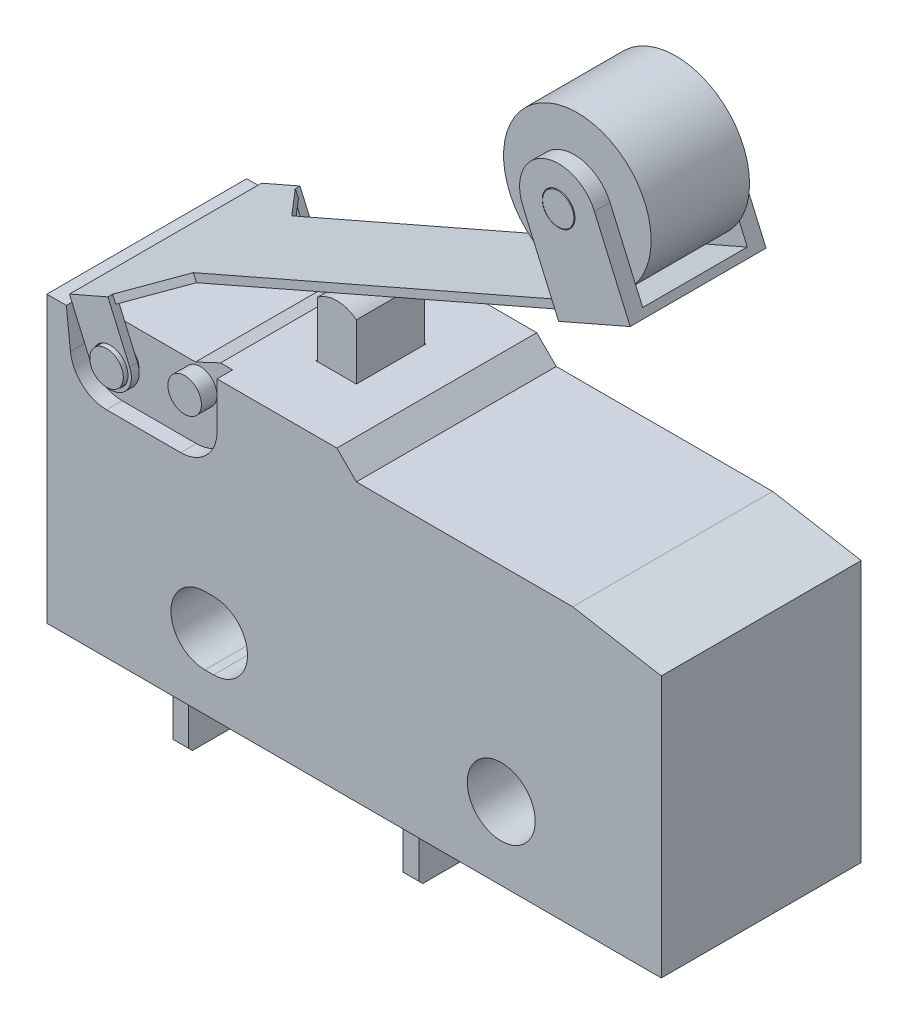
SolidWorks part; units mm, degrees
ref_plane "Front" through (0, 0, 0) normal (0, 0, 1) x (1, 0, 0)
ref_plane "Top" through (0, 0, 0) normal (0, 1, 0) x (1, 0, 0)
ref_plane "Right" through (0, 0, 0) normal (1, 0, 0) x (0, 0, -1)
sketch "Sketch2" plane through (0, 0, 0) normal (0, 0, 1) x (1, 0, 0)
  line L0 (-4.8514, 3.4671) -> (-4.572, 3.4671)
  line L1 (9.9949, 8.509) -> (7.1139, 9.017)
  line L2 (-9.9949, 9.271) -> (-9.9949, 0)
  line L3 (-9.9949, 0) -> (9.9949, 0)
  line L4 (9.9949, 8.509) -> (9.9949, 0)
  line L5 (-4.8514, 1.2573) -> (-4.572, 1.2573)
  line L6 (-4.7117, 3.4671) -> (-4.7117, 1.2573) construction
  line L7 (4.7879, 2.3622) -> (-4.572, 2.3622) construction
  line L8 (7.1139, 9.017) -> (0.0762, 9.017)
  line L9 (0.0762, 9.017) -> (-0.5588, 9.652)
  line L10 (-0.5588, 9.652) -> (-4.8514, 9.652)
  line L11 (-4.8514, 9.652) -> (-5.6646, 9.271)
  line L12 (-5.6646, 9.271) -> (-9.9949, 9.271)
  line L13 (-2.7051, 9.652) -> (-2.7051, 2.3622) construction
  line L14 (-4.8514, 9.652) -> (-4.8514, 3.4671) construction
  circle A0 centre (4.7879, 2.3622) radius 1.1049
  arc A1 (-4.8514, 3.4671) -> (-4.8514, 1.2573) centre (-4.8514, 2.3622) ccw
  arc A2 (-4.572, 1.2573) -> (-4.572, 3.4671) centre (-4.572, 2.3622) ccw
  dimension "D4" = 5.207
  dimension "D5" = 2.2098
  dimension "D6" = 2.4892
  dimension "D7" = 6.6548
  dimension "D8" = 7.2898
  dimension "D9" = 7.493
  dimension "D13" = 6.9088
  dimension "D1" = 19.9898
  dimension "D2" = 2.3622
  dimension "D3" = 9.4996
  dimension "D10" = 0.508
  dimension "D11" = 10
  dimension "D12" = 135
extrude "Extrude1" add sketch "Sketch2" along normal mid plane 6.5024
sketch "Sketch3" plane through (0, 0, 0) normal (0, 0, 1) x (1, 0, 0)
  line L0 (-3.3401, 9.271) -> (-3.3401, 11.4357)
  line L1 (-2.7051, 9.271) -> (-2.7051, 10.6426) construction
  line L2 (-2.0701, 11.4357) -> (-2.0701, 9.271)
  line L3 (-2.0701, 9.271) -> (-3.3401, 9.271)
  line L4 (-3.3401, 11.4357) -> (-2.0701, 11.4357) construction
  line L5 (-2.7051, 9.652) -> (-2.7051, 2.3622) construction
  line L6 (-5.6646, 9.271) -> (-9.9949, 9.271) construction
  arc A0 (-3.3401, 11.4357) -> (-2.0701, 11.4357) centre (-2.7051, 10.6426) cw
  arc A1 (-4.8514, 3.4671) -> (-4.8514, 1.2573) centre (-4.8514, 2.3622) ccw construction
  dimension "D1" = 9.2964
  dimension "D3" = 1.016
  dimension "D2" = 1.27
extrude "Extrude2" add sketch "Sketch3" along normal mid plane 2.2098 separate body
sketch "Sketch4" plane through (0, 9.652, 0) normal (0, 1, 0) x (-1, 0, 0)
  line L0 (2.0701, -1.1049) -> (3.3401, -1.1049) construction
  line L1 (3.3401, 1.1049) -> (3.3401, -1.1049) construction
  line L2 (2.0701, 1.1049) -> (2.0701, -1.1049) construction
  line L3 (3.3401, 1.1049) -> (2.0701, 1.1049) construction
  line L4 (2.0701, -1.1049) -> (3.3401, -1.1049) construction
  line L5 (3.3401, 1.1049) -> (3.3401, -1.1049) construction
  line L6 (2.0701, 1.1049) -> (2.0701, -1.1049) construction
  line L7 (3.3401, 1.1049) -> (2.0701, 1.1049) construction
  line L8 (3.3655, 1.1303) -> (3.3655, -1.1303)
  line L9 (2.0447, -1.1303) -> (3.3655, -1.1303)
  line L10 (2.0447, 1.1303) -> (2.0447, -1.1303)
  line L11 (3.3655, 1.1303) -> (2.0447, 1.1303)
  dimension "D1" = 0.0254
extrude "Cut-Extrude1" cut sketch "Sketch4" against normal blind 1.016
sketch "Sketch5" plane through (0, 0, 3.2512) normal (0, 0, 1) x (1, 0, 0)
  line L0 (-9.2329, 9.271) -> (-9.2329, 8.1661) construction
  line L1 (-8.0518, 6.985) -> (-5.6388, 6.985)
  line L2 (-4.4577, 8.1661) -> (-4.4577, 9.652)
  line L3 (-5.6646, 9.271) -> (-9.9949, 9.271) construction
  line L4 (-4.8514, 9.652) -> (-5.6646, 9.271) construction
  line L5 (-0.5588, 9.652) -> (-4.8514, 9.652) construction
  line L6 (-5.6646, 9.271) -> (-9.2329, 9.271)
  line L7 (-4.8514, 9.652) -> (-5.6646, 9.271)
  line L8 (-4.4577, 9.652) -> (-4.8514, 9.652)
  line L9 (-9.9949, 9.271) -> (-9.9949, 0) construction
  line L11 (-5.6646, 9.271) -> (-9.9949, 9.271) construction
  line L12 (-9.3599, 9.271) -> (-9.226, 8.0385)
  line L13 (-9.3599, 9.271) -> (-9.2329, 9.271)
  circle A0 centre (-5.5118, 8.6741) radius 0.5461
  circle A1 centre (-8.0518, 8.1661) radius 0.5461
  arc A2 (-9.226, 8.0385) -> (-8.0518, 6.985) centre (-8.0518, 8.1661) ccw
  arc A3 (-5.6388, 6.985) -> (-4.4577, 8.1661) centre (-5.6388, 8.1661) ccw
  dimension "D4" = 0.0508
  dimension "D5" = 1.0922
  dimension "D6" = 2.54
  dimension "D7" = 0.508
  dimension "D1" = 0.762
  dimension "D2" = 0.508
  dimension "D3" = 0.635
  dimension "D8" = 0.127
extrude "Cut-Extrude2" cut sketch "Sketch5" against normal blind 0.508
mirror "Mirror1" about plane through (0, 0, 0) normal (0, 0, 1) of "Cut-Extrude2"
ref_plane "Plane1" through (-7.493, 0, 0) normal (1, 0, 0) x (0, 0, -1)
sketch "Sketch10" plane through (-7.493, 0, 0) normal (1, 0, 0) x (0, 0, -1)
  line L0 (-1.397, 0) -> (-1.397, -3.0734)
  line L1 (-1.27, -3.2004) -> (1.27, -3.2004)
  line L2 (1.397, -3.0734) -> (1.397, 0)
  line L3 (1.397, 0) -> (-1.397, 0)
  line L4 (0, -3.2004) -> (0, -1.7018) construction
  line L5 (0, 0) -> (0, -1.7018) construction
  line L6 (-1.397, -3.0734) -> (-1.27, -3.2004)
  line L7 (1.27, -3.2004) -> (1.397, -3.0734)
  circle A0 centre (0, -1.7018) radius 0.9017
  point P1 (-1.397, -3.2004)
  point P3 (1.397, -3.2004)
  dimension "D2" = 1.8034
  dimension "D1" = 3.2004
  dimension "D3" = 2.794
  dimension "D4" = 1.4986
  dimension "D5" = 0.127
  dimension "D6" = 45
  dimension "D7" = 0.127
  dimension "D8" = 45
extrude "Extrude6" add sketch "Sketch10" along normal mid plane 0.508
pattern_linear "LPattern1" count 2 spacing 7.493 along (1, 0, 0) of "Extrude6"
sketch "Sketch6" plane through (0, 0, 0) normal (0, 0, 1) x (1, 0, 0)
  line L0 (-9.2837, 9.2815) -> (7.9412, 16.8042)
  line L1 (7.9412, 16.8042) -> (7.8396, 17.037)
  line L2 (7.8396, 17.037) -> (-9.3854, 9.5142)
  line L3 (-9.3854, 9.5142) -> (-9.2837, 9.2815)
  line L6 (5.5119, 16.0204) -> (4.4496, 18.4528) construction
  line L7 (6.7772, 19.4694) -> (7.8396, 17.037) construction
  line L10 (-9.2837, 9.2815) -> (-8.6773, 7.8929) construction
  line L11 (-7.4263, 8.4393) -> (-8.0327, 9.8278) construction
  circle A0 centre (-8.0518, 8.1661) radius 0.5461 construction
  circle A2 centre (5.6134, 18.9611) radius 2.4003 construction
  arc A6 (-8.6773, 7.8929) -> (-7.4263, 8.4393) centre (-8.0518, 8.1661) ccw construction
  circle A7 centre (4.7879, 2.3622) radius 1.1049 construction
  arc A8 (4.4496, 18.4528) -> (6.7772, 19.4694) centre (5.6134, 18.9611) cw construction
  dimension "D1" = 4.8006
  dimension "D2" = 18.9992
  dimension "D3" = 0.0762
  dimension "D6" = 2.54
  dimension "D4" = 0.8255
  dimension "D5" = 0.254
  dimension "D7" = 0.254
  dimension "D8" = 17.526
extrude "Extrude3" add sketch "Sketch6" along normal mid plane 3.2004 separate body
sketch "Sketch8" plane through (0, 0, 3.2512) normal (0, 0, 1) x (1, 0, 0)
  line L0 (-7.4263, 8.4393) -> (-8.0327, 9.8278) construction
  line L1 (-9.2837, 9.2815) -> (-8.6773, 7.8929) construction
  line L2 (-7.4263, 8.4393) -> (-8.1344, 10.0606)
  line L3 (-9.3854, 9.5142) -> (-8.6773, 7.8929)
  line L4 (7.8396, 17.037) -> (-9.3854, 9.5142) construction
  line L5 (-8.1344, 10.0606) -> (-9.3854, 9.5142)
  line L6 (7.8396, 17.037) -> (-9.3854, 9.5142) construction
  arc A0 (-8.6773, 7.8929) -> (-7.4263, 8.4393) centre (-8.0518, 8.1661) ccw construction
  arc A1 (-8.6773, 7.8929) -> (-7.4263, 8.4393) centre (-8.0518, 8.1661) ccw
  circle A5 centre (-8.0518, 8.1661) radius 0.5715
  circle A6 centre (-8.0518, 8.1661) radius 0.5715
  dimension "D1" = 0.0254
extrude "Extrude4" add sketch "Sketch8" against normal blind 0.254 from offset 0.127 separate body offset against normal yes
sketch "Sketch9" plane through (0, 0, 1.6002) normal (0, 0, 1) x (1, 0, 0)
  line L1 (-9.3854, 9.5142) -> (-9.2837, 9.2815) construction
  line L2 (-9.2837, 9.2815) -> (7.9412, 16.8042) construction
  line L3 (7.8396, 17.037) -> (-9.3854, 9.5142) construction
  line L4 (-8.0327, 9.8278) -> (-8.1344, 10.0606)
  line L5 (-9.3854, 9.5142) -> (-9.2837, 9.2815)
  line L6 (-9.2837, 9.2815) -> (-8.0327, 9.8278)
  line L7 (-8.1344, 10.0606) -> (-9.3854, 9.5142)
  line L8 (-9.2837, 9.2815) -> (7.9412, 16.8042) construction
  line L10 (-7.4263, 8.4393) -> (-8.1344, 10.0606) construction
extrude "Extrude5" add sketch "Sketch9" along normal up to surface (1.27 mm away) up to face at (-7.4803, 8.1661, 2.8702)
mirror "Mirror7" about plane through (0, 0, 0) normal (0, 0, 1) of bodies 116
combine bodies "Combine1" operation type add bodies to combine 118 114 116
sketch "Sketch11" plane through (0, 0, 0) normal (0, 0, 1) x (1, 0, 0)
  circle A0 centre (5.6134, 18.9611) radius 2.4003 construction
  circle A1 centre (5.6134, 18.9611) radius 2.4003
extrude "Extrude7" add sketch "Sketch11" along normal mid plane 3.2004
sketch "Sketch12" plane through (0, 0, 0) normal (0, 0, 1) x (1, 0, 0)
  circle A0 centre (5.6134, 18.9611) radius 0.508
  dimension "D1" = 1.016
extrude "Extrude8" add sketch "Sketch12" along normal mid plane 4.445
sketch "Sketch13" plane through (0, 0, 1.6002) normal (0, 0, 1) x (1, 0, 0)
  line L0 (-9.2837, 9.2815) -> (7.9412, 16.8042) construction
  line L1 (6.7772, 19.4694) -> (7.8396, 17.037) construction
  line L2 (5.5119, 16.0204) -> (4.4496, 18.4528) construction
  line L3 (5.6135, 15.7876) -> (7.9412, 16.8042)
  line L4 (6.7772, 19.4694) -> (7.9412, 16.8042)
  line L5 (5.6135, 15.7876) -> (4.4496, 18.4528)
  line L6 (5.6134, 18.9611) -> (5.6134, 19.4691) construction
  line L7 (5.6134, 19.4691) -> (5.6134, 19.4945) construction
  circle A0 centre (5.6134, 18.9611) radius 0.508 construction
  arc A1 (6.7772, 19.4694) -> (4.4496, 18.4528) centre (5.6134, 18.9611) ccw construction
  circle A2 centre (5.6134, 18.9611) radius 0.508 construction
  arc A3 (6.7772, 19.4694) -> (4.4496, 18.4528) centre (5.6134, 18.9611) ccw
  circle A4 centre (5.6134, 18.9611) radius 0.5334
  dimension "D1" = 0.0254
extrude "Extrude9" add sketch "Sketch13" along normal blind 0.508 from offset 0.1016 separate body
mirror "Mirror8" about plane through (0, 0, 0) normal (0, 0, 1) of bodies 124
sketch "Sketch14" plane through (0, 0, 0) normal (0, 0, 1) x (1, 0, 0)
  line L0 (5.5119, 16.0204) -> (4.4496, 18.4528) construction
  line L1 (7.9412, 16.8042) -> (7.8396, 17.037) construction
  line L2 (-9.2837, 9.2815) -> (7.9412, 16.8042) construction
  line L3 (7.8396, 17.037) -> (-9.3854, 9.5142) construction
  line L4 (5.6135, 15.7876) -> (5.5119, 16.0204)
  line L5 (7.9412, 16.8042) -> (7.8396, 17.037)
  line L6 (5.6135, 15.7876) -> (7.9412, 16.8042)
  line L7 (7.8396, 17.037) -> (5.5119, 16.0204)
extrude "Extrude10" add sketch "Sketch14" along normal up to vertex (2.2098 mm away) and the other way up to vertex (2.2098 mm away) up to point (7.9412, 16.8042, 2.2098) other way up to point (7.9412, 16.8042, -2.2098)
chamfer "Chamfer1" distance 1.3716 angle 45 2 edges
sketch "Sketch15" plane through (0, 0, 0) normal (0, 0, 1) x (1, 0, 0)
  line L0 (9.3628, 8.1661) -> (9.3628, 20.7376) construction
  line L1 (9.3628, 20.7376) -> (3.9992, 20.7376) construction
  line L2 (-8.0518, 8.1661) -> (3.9992, 20.7376) construction
  line L3 (-8.0518, 8.1661) -> (6.9925, 16.9376) construction
  line L4 (6.9925, 16.9376) -> (9.3628, 16.9376) construction
  line L5 (-8.0518, 8.1661) -> (7.3794, 16.2376) construction
  line L6 (7.3794, 16.2376) -> (9.3628, 16.2376) construction
  line L7 (-8.0518, 8.1661) -> (8.0754, 14.7376) construction
  line L8 (8.0754, 14.7376) -> (9.3628, 14.7376) construction
  circle A0 centre (5.6134, 18.9611) radius 2.4003
  circle A1 centre (8.0557, 14.7856) radius 2.4003 construction
  circle A2 centre (8.3427, 14.0391) radius 2.4003 construction
  circle A3 centre (8.8258, 12.4576) radius 2.4003 construction
  arc A4 (9.3628, 8.1661) -> (3.9992, 20.7376) centre (-8.0518, 8.1661) ccw construction
  circle A5 centre (5.6134, 18.9611) radius 2.4003 construction
  point P11 (3.9992, 20.7376)
  dimension "D1" = 4.5
  dimension "D2" = 0.7
  dimension "D3" = 1.5
sketch "Sketch16" plane through (0, 0, 0) normal (0, 0, 1) x (1, 0, 0)
  circle A0 centre (8.0557, 14.7856) radius 2.4003 construction
  circle A1 centre (8.3427, 14.0391) radius 2.4003 construction
  circle A2 centre (8.8258, 12.4576) radius 2.4003 construction
  circle A3 centre (8.0557, 14.7856) radius 2.4003 construction
  circle A4 centre (8.3427, 14.0391) radius 2.4003 construction
  circle A5 centre (8.8258, 12.4576) radius 2.4003 construction
  point P9 (8.0754, 14.7376)
  point P10 (7.3794, 16.2376)
  point P12 (6.9925, 16.9376)
  point P14 (3.9992, 20.7376)
